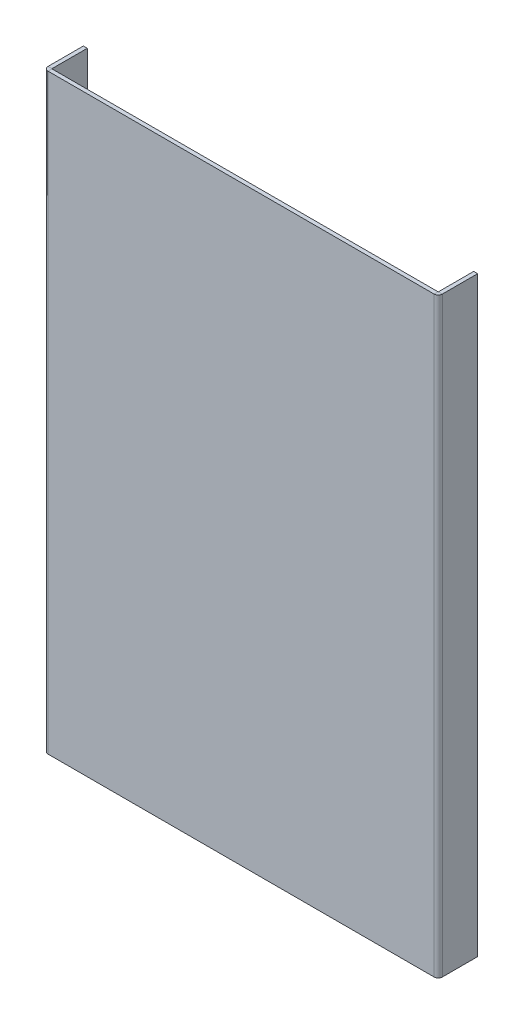
SolidWorks part; units mm, degrees
note: The reader was unsure of these and kept them because the rebuilt part matched: flange length of "边线-法兰1".
ref_plane "前视基准面" through (0, 0, 0) normal (0, 0, 1) x (1, 0, 0)
ref_plane "上视基准面" through (0, 0, 0) normal (0, 1, 0) x (1, 0, 0)
ref_plane "右视基准面" through (0, 0, 0) normal (1, 0, 0) x (0, 0, -1)
sketch "草图1" plane through (0, 0, 0) normal (0, 0, 1) x (1, 0, 0)
  line L1 (-100, -150) -> (100, -150)
  line L2 (-100, -150) -> (-100, 150)
  line L3 (-100, 150) -> (100, 150)
  line L4 (100, -150) -> (100, 150)
  line L5 (-100, -150) -> (100, 150) construction
  line L6 (-100, 150) -> (100, -150) construction
  point P0 (0, 0)
  dimension "D1" = 300
  dimension "D2" = 200
base flange "基体-法兰1" sketch "草图1" thickness 2 reverse thickness direction no parameters "D1"=0.1
edge flange "边线-法兰1" sketch "草图10" flange profiles "草图10", "草图11" flange angle 90 flange length 20 flange position material inside bend radius 0.1 thickness 2 relief rectangular parameters "D6"=10, "D8"=0.5
sketch "草图10" plane through (100, 0, -2) normal (-1, 0, 0) x (0, 1, 0)
  line L2 (-150, 0) -> (-150, 18)
  line L3 (-150, 18) -> (150, 18)
  line L4 (150, 18) -> (150, 0)
  line L5 (150, 0) -> (-150, 0) construction
  line L6 (150, 0) -> (-150, 0)
sketch "草图11" plane through (-100, 0, -2) normal (1, 0, 0) x (0, -1, 0)
  line L0 (150, 0) -> (-150, 0) construction
  line L1 (150, 0) -> (-150, 0)
  line L2 (150, 0) -> (150, 18)
  line L3 (150, 18) -> (-150, 18)
  line L4 (-150, 18) -> (-150, 0)
bend "边线折弯1" bend radius 0.1 bend angle 90 parameters "D5"=1
bend "边线折弯2" bend radius 0.1 bend angle 90 parameters "D5"=2
sketch "折弯-线1" [suppressed] plane through (0, 0, 0) normal (0, 1, 0) x (1, 0, 0)
sketch "边界框1" [suppressed] plane through (0, 0, 0) normal (0, 1, 0) x (1, 0, 0)
sheet metal parameters "钣金6" thickness 2 parameters "D1"=0.1
flat pattern "平板型式6" [suppressed]
sketch "折弯-线2" plane through (0, 0, 0) normal (0, 1, 0) x (1, 0, 0)
sketch "边界框2" [suppressed] plane through (0, 0, 0) normal (0, 1, 0) x (1, 0, 0)
sheet metal parameters "钣金7" thickness 2 parameters "D1"=0.1
flat pattern "平板型式6"
sketch "折弯-线2" plane through (0, 0, 0) normal (0, 0, 1) x (1, 0, 0)
  line L0 (-98.2, 150) -> (-98.2, -150) construction
  line L1 (98.2, -150) -> (98.2, 150) construction
  line L2 (-98.2, 150) -> (-98.2, -150) construction
  line L3 (98.2, -150) -> (98.2, 150) construction
sketch3d "边界框2" [suppressed]
  line L0 (116.4, 150, 0) -> (116.4, -150, 0) construction
  line L1 (-116.4, 150, 0) -> (-116.4, -150, 0) construction
  line L2 (116.4, 150, 0) -> (-116.4, 150, 0) construction
  line L3 (116.4, -150, 0) -> (-116.4, -150, 0) construction
bend of the flat pattern "展平-<边线折弯1>1"
bend of the flat pattern "展平-<边线折弯2>1"
